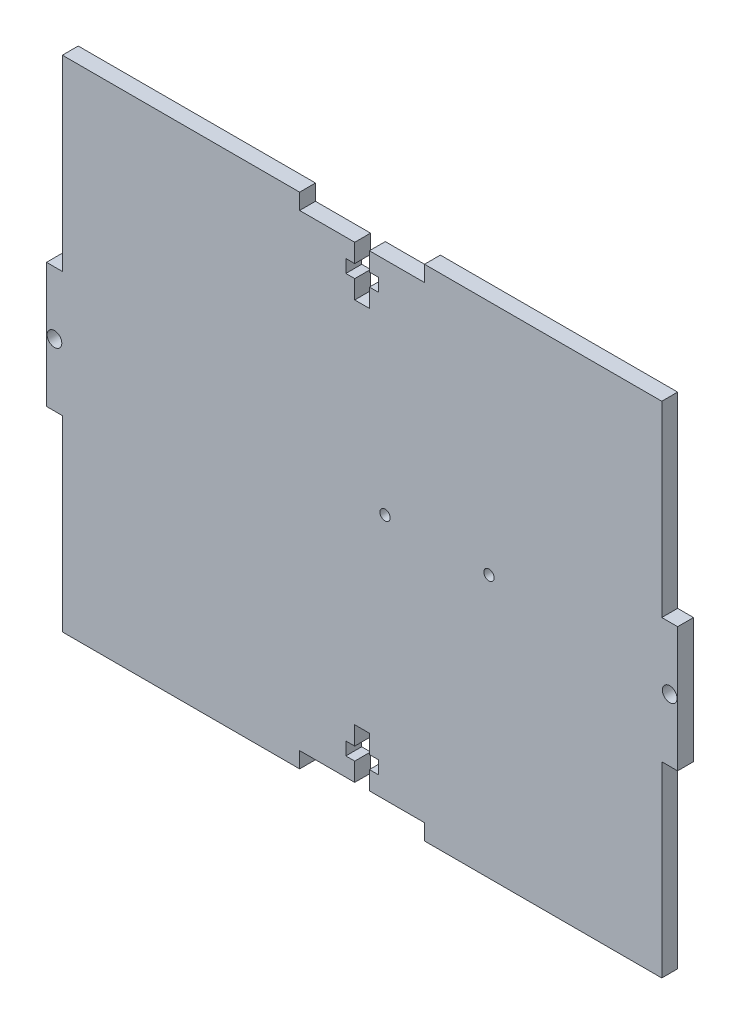
SolidWorks part; units mm, degrees
ref_plane "Front Plane" through (0, 0, 0) normal (0, 0, 1) x (1, 0, 0)
ref_plane "Top Plane" through (0, 0, 0) normal (0, 1, 0) x (1, 0, 0)
ref_plane "Right Plane" through (0, 0, 0) normal (1, 0, 0) x (0, 0, -1)
sketch "Sketch1" plane through (0, 0, 0) normal (0, 0, 1) x (1, 0, 0)
  line L0 (0, 50) -> (0, -50) construction
  line L1 (-60, 50) -> (60, 50)
  line L2 (-60, 50) -> (-60, -50)
  line L3 (-60, -50) -> (60, -50)
  line L4 (60, 50) -> (60, -50)
  line L5 (-60, 50) -> (60, -50) construction
  line L6 (-60, -50) -> (60, 50) construction
  line L7 (-60, 0) -> (60, 0) construction
  line L8 (-3.25, -40.525) -> (3.25, -40.525)
  line L9 (12.5, 50) -> (-12.5, 50)
  line L10 (12.5, 50) -> (12.5, 46.825)
  line L11 (12.5, 46.825) -> (-12.5, 46.825)
  line L12 (-12.5, 50) -> (-12.5, 46.825)
  line L13 (12.5, 50) -> (-12.5, 46.825) construction
  line L14 (12.5, 46.825) -> (-12.5, 50) construction
  line L15 (-1.47, 46.825) -> (1.47, 46.825)
  line L16 (-1.47, 46.825) -> (-1.47, 36.825)
  line L17 (-1.47, 36.825) -> (1.47, 36.825)
  line L18 (1.47, 46.825) -> (1.47, 36.825)
  line L19 (-1.47, 46.825) -> (1.47, 36.825) construction
  line L20 (-1.47, 36.825) -> (1.47, 46.825) construction
  line L21 (-3.25, 43.125) -> (3.25, 43.125)
  line L22 (-3.25, 43.125) -> (-3.25, 40.525)
  line L23 (-3.25, 40.525) -> (3.25, 40.525)
  line L24 (3.25, 43.125) -> (3.25, 40.525)
  line L25 (-3.25, 43.125) -> (3.25, 40.525) construction
  line L26 (-3.25, 40.525) -> (3.25, 43.125) construction
  line L27 (3.25, -43.125) -> (3.25, -40.525)
  line L28 (-3.25, -43.125) -> (3.25, -43.125)
  line L29 (-3.25, -43.125) -> (-3.25, -40.525)
  line L30 (-1.47, -36.825) -> (1.47, -36.825)
  line L31 (1.47, -46.825) -> (1.47, -36.825)
  line L32 (-1.47, -46.825) -> (1.47, -46.825)
  line L33 (-1.47, -46.825) -> (-1.47, -36.825)
  line L34 (12.5, -46.825) -> (-12.5, -46.825)
  line L35 (-12.5, -50) -> (-12.5, -46.825)
  line L36 (12.5, -50) -> (-12.5, -50)
  line L37 (12.5, -50) -> (12.5, -46.825)
  line L38 (63.175, -12.5) -> (60, -12.5)
  line L39 (-63.175, 12.5) -> (-60, 12.5)
  line L40 (-63.175, 12.5) -> (-63.175, -12.5)
  line L41 (-63.175, -12.5) -> (-60, -12.5)
  line L42 (-60, 12.5) -> (-60, -12.5)
  line L43 (-63.175, 12.5) -> (-60, -12.5) construction
  line L44 (-63.175, -12.5) -> (-60, 12.5) construction
  line L45 (60, 12.5) -> (60, -12.5)
  line L46 (63.175, 12.5) -> (60, 12.5)
  line L47 (63.175, 12.5) -> (63.175, -12.5)
  circle A0 centre (-61.5875, 0) radius 1.47
  circle A1 centre (61.5875, 0) radius 1.47
  circle A3 centre (25.4, 2.575) radius 1.0287
  circle A4 centre (4.6, 2.575) radius 1.0287
  point P0 (0, 0)
  point P10 (0, 48.4125)
  point P15 (0, 41.825)
  point P20 (0, 41.825)
  point P37 (-61.5875, 0)
  dimension "D11" = 2.94
  dimension "D1" = 100
  dimension "D2" = 120
  dimension "D3" = 3.175
  dimension "D4" = 10
  dimension "D5" = 2.94
  dimension "D6" = 25
  dimension "D7" = 6.5
  dimension "D8" = 2.6
  dimension "D9" = 6.3
  dimension "D10" = 3.175
extrude "Boss-Extrude1" add sketch "Sketch1" along normal mid plane 3.175 contours L21 L24 L23 L18 L17 L16 L22 L11 L12 L1 L2 L3 L4 L10 | L40 L39 L42 L41 | A0 | L38 L45 L46 L47 | A1 region at (-0.0085, -0.0015, 0)
